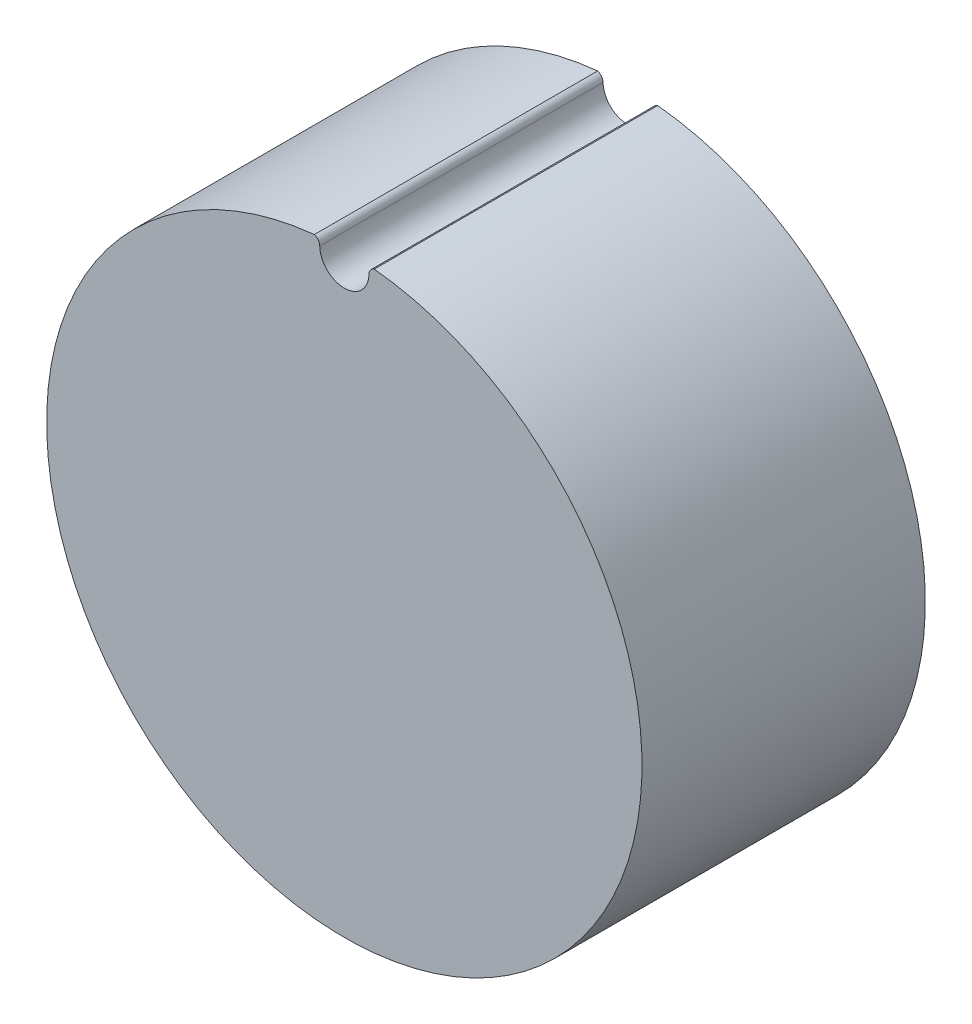
SolidWorks part; units mm, degrees
material "6061 合金"
ref_plane "前基準面" through (0, 0, 0) normal (0, 0, 1) x (1, 0, 0)
ref_plane "上基準面" through (0, 0, 0) normal (0, 1, 0) x (1, 0, 0)
ref_plane "右基準面" through (0, 0, 0) normal (1, 0, 0) x (0, 0, -1)
sketch "草圖1" plane through (0, 0, 0) normal (0, 0, 1) x (1, 0, 0)
  circle A0 centre (0, 0) radius 11.555
  dimension "D1" = 23.11
extrude "填料-伸長1" add sketch "草圖1" along normal blind 11
sketch "草圖2" plane through (0, 0, 11) normal (0, 0, 1) x (1, 0, 0)
  line L0 (-1.4082, 11.4689) -> (0, 0) construction
  line L1 (0, 0) -> (1.4082, 11.4689) construction
  arc A0 (-1.4082, 11.4689) -> (1.4082, 11.4689) centre (0, 0) cw
  circle A1 centre (0, 0) radius 11.555 construction
  arc A2 (-0.955, 11.2155) -> (0.955, 11.2155) centre (0, 11.2301) ccw
  arc A3 (-1.4082, 11.4689) -> (-0.955, 11.2155) centre (-1.255, 11.211) cw
  arc A4 (1.4082, 11.4689) -> (0.955, 11.2155) centre (1.255, 11.211) ccw
  point P12 (0, 11.555)
  point P13 (0, 10.275)
  dimension "D1" = 0.3
  dimension "D2" = 0.3
  dimension "D3" = 1.28
  dimension "D4" = 1.91
  dimension "D5" = 14
extrude "除料-伸長1" cut sketch "草圖2" against normal up to next contours A4 A0 A3 A2 region at (0, 10.9973, 11)
